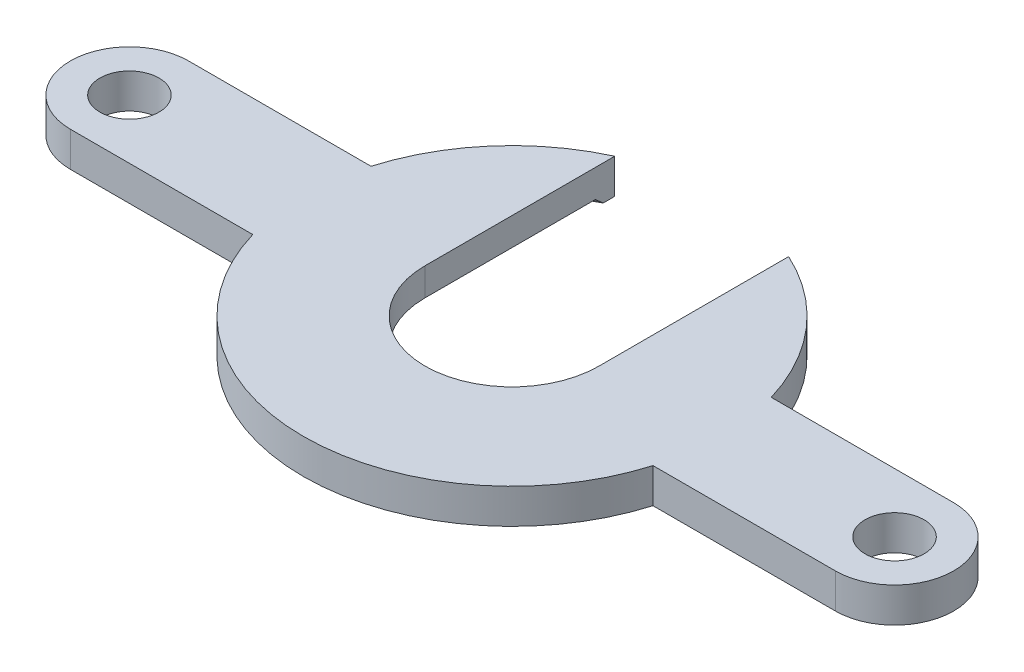
SolidWorks part; units mm, degrees
ref_plane "Front Plane" through (0, 0, 0) normal (0, 0, 1) x (1, 0, 0)
ref_plane "Top Plane" through (0, 0, 0) normal (0, 1, 0) x (1, 0, 0)
ref_plane "Right Plane" through (0, 0, 0) normal (1, 0, 0) x (0, 0, -1)
sketch "Sketch1" plane through (0, 0, 0) normal (0, 1, 0) x (1, 0, 0)
  line L0 (-55, 0) -> (55, 0) construction
  line L1 (55, 8.5) -> (28.7706, 8.5)
  line L2 (63.5, 0) -> (63.5, -8.5) construction
  line L3 (55, -8.5) -> (28.7706, -8.5)
  line L4 (-63.5, 0) -> (-63.5, -8.5) construction
  line L5 (-55, 0) -> (63.5, 0) construction
  line L6 (55, 0) -> (-63.5, 0) construction
  line L7 (-12.5, 0) -> (-12.5, 27.2718)
  line L8 (12.5, 0) -> (12.5, 27.2718)
  line L9 (-12.5, 8.5) -> (12.5, 8.5) construction
  line L10 (28.7706, 8.5) -> (12.5, 8.5) construction
  line L11 (-28.7706, 8.5) -> (-12.5, 8.5) construction
  line L12 (12.5, 8.5) -> (28.7706, 8.5) construction
  line L13 (-28.7706, -8.5) -> (28.7706, -8.5) construction
  line L14 (28.7706, -8.5) -> (9.1652, -8.5) construction
  line L15 (9.1652, 8.5) -> (-9.1652, 8.5) construction
  line L16 (-9.1652, 8.5) -> (-12.5, 8.5) construction
  line L17 (9.1652, 8.5) -> (-9.1652, 8.5) construction
  line L18 (-9.1652, 8.5) -> (-12.5, 8.5) construction
  line L19 (-12.5, 8.5) -> (-28.7706, 8.5) construction
  line L20 (-12.5, 8.5) -> (-28.7706, 8.5) construction
  line L21 (-28.7706, 8.5) -> (-55, 8.5)
  line L22 (12.5, 8.5) -> (9.1652, 8.5) construction
  line L23 (12.5, 8.5) -> (9.1652, 8.5) construction
  line L24 (28.7706, 8.5) -> (12.5, 8.5) construction
  line L25 (-9.1652, -8.5) -> (-28.7706, -8.5) construction
  line L26 (-28.7706, -8.5) -> (-55, -8.5)
  line L27 (-9.1652, -8.5) -> (-28.7706, -8.5) construction
  line L28 (9.1652, -8.5) -> (-9.1652, -8.5) construction
  line L29 (9.1652, -8.5) -> (-9.1652, -8.5) construction
  line L30 (28.7706, -8.5) -> (9.1652, -8.5) construction
  line L31 (63.5, 8.5) -> (55, 8.5) construction
  line L32 (63.5, 8.5) -> (63.5, 0) construction
  line L33 (63.5, -8.5) -> (55, -8.5) construction
  line L34 (-55, 8.5) -> (-63.5, 8.5) construction
  line L35 (-63.5, 8.5) -> (-63.5, 0) construction
  line L36 (-55, -8.5) -> (-63.5, -8.5) construction
  arc A0 (-12.5, 27.2718) -> (-28.7706, 8.5) centre (0, 0) ccw
  arc A1 (-12.5, 0) -> (12.5, 0) centre (0, 0) ccw
  circle A2 centre (-55, 0) radius 4.25
  circle A3 centre (55, 0) radius 4.25
  arc A4 (12.5, 27.2718) -> (-12.5, 27.2718) centre (0, 0) ccw construction
  arc A5 (12.5, 0) -> (-12.5, 0) centre (0, 0) ccw construction
  arc A6 (30, 0) -> (28.7706, 8.5) centre (0, 0) ccw construction
  arc A7 (28.7706, 8.5) -> (12.5, 27.2718) centre (0, 0) ccw
  arc A8 (28.7706, -8.5) -> (30, 0) centre (0, 0) ccw construction
  arc A9 (-28.7706, 8.5) -> (-30, 0) centre (0, 0) ccw construction
  arc A10 (-28.7706, -8.5) -> (28.7706, -8.5) centre (0, 0) ccw
  arc A11 (-30, 0) -> (-28.7706, -8.5) centre (0, 0) ccw construction
  arc A12 (-55, -8.5) -> (-55, 8.5) centre (-55, 0) cw
  arc A13 (55, 8.5) -> (55, -8.5) centre (55, 0) cw
  dimension "D1" = 60
  dimension "D2" = 25
  dimension "D4" = 8.5
  dimension "D3" = 55
  dimension "D5" = 8.5
  dimension "D6" = 17
extrude "Boss-Extrude1" add sketch "Sketch1" along normal blind 5
sketch "Sketch2" plane through (0, 0, 0) normal (0, 1, 0) x (1, 0, 0)
  circle A0 centre (0, 0) radius 27.5
  dimension "D1" = 55
extrude "Cut-Extrude1" cut sketch "Sketch2" along normal blind 1
chamfer "Chamfer1" distance 1 angle 45 1 edges at (0, 0, 27.5)
